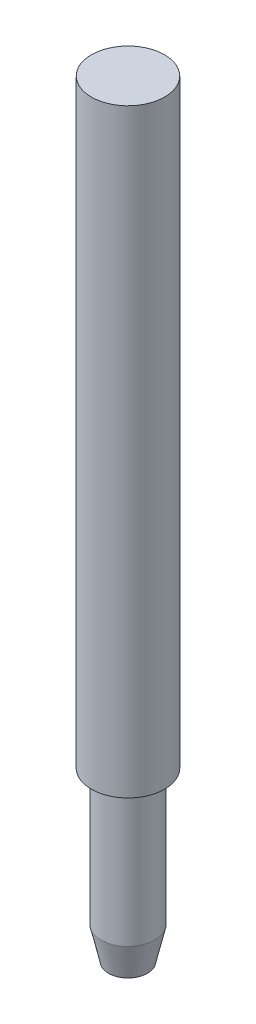
SolidWorks part; units mm, degrees
material "6061 Alloy"
ref_plane "Front Plane" through (0, 0, 0) normal (0, 0, 1) x (1, 0, 0)
ref_plane "Top Plane" through (0, 0, 0) normal (0, 1, 0) x (1, 0, 0)
ref_plane "Right Plane" through (0, 0, 0) normal (1, 0, 0) x (0, 0, -1)
sketch "Sketch1" plane through (0, 0, 0) normal (0, 1, 0) x (1, 0, 0)
  circle A0 centre (0, 0) radius 2.3813
  dimension "D1" = 4.7625
extrude "Boss-Extrude1" add sketch "Sketch1" along normal blind 38.9763
sketch "Sketch2" plane through (0, 0, 0) normal (0, -1, 0) x (1, 0, 0)
  circle A0 centre (0, 0) radius 1.7526
  dimension "D1" = 3.5052
extrude "Boss-Extrude2" add sketch "Sketch2" along normal blind 10.922
sketch "Sketch3" plane through (0, 0, 0) normal (1, 0, 0) x (0, 0, -1)
  line L0 (-1.7526, -10.922) -> (1.7526, -10.922) construction
  line L1 (-1.7526, -10.922) -> (1.7526, -10.922)
  line L2 (1.27, -10.922) -> (1.7526, -8.8053)
  line L3 (1.7526, -10.922) -> (1.7526, 0) construction
  line L4 (-1.27, -10.922) -> (-1.7526, -8.8053)
  line L5 (-1.7526, 0) -> (-1.7526, -10.922) construction
  line L6 (1.7526, -8.8053) -> (1.7526, -10.922)
  line L7 (0, -10.922) -> (0, -5.3561) construction
  dimension "D1" = 2.1167
  dimension "D2" = 2.54
  dimension "D3" = 3.5052
  dimension "D4" = 0.4826
revolve "Cut-Revolve1" cut sketch "Sketch3" angle 360 about L7 region at (0, -10.2164, -1.5917) reverse direction yes
equation "\"D1@Sketch3\"=2/24"
equation "\"D4@Sketch3\"=(\"D3@Sketch3\"-\"D2@Sketch3\")/2"
equation "\"D1@Boss-Extrude2\"=0.450000in-0.02"
